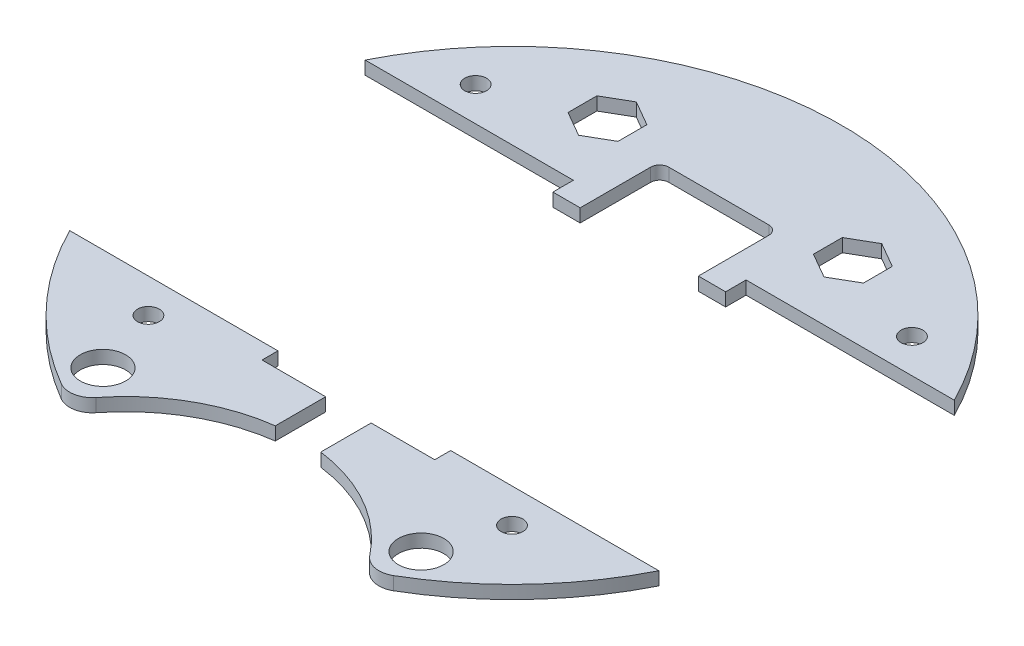
SolidWorks part; units mm, degrees
material "Acrylic (Medium-high impact)"
ref_plane "Front Plane" through (0, 0, 0) normal (0, 0, 1) x (1, 0, 0)
ref_plane "Top Plane" through (0, 0, 0) normal (0, 1, 0) x (1, 0, 0)
ref_plane "Right Plane" through (0, 0, 0) normal (1, 0, 0) x (0, 0, -1)
sketch "Sketch1" plane through (0, 0, 0) normal (0, 1, 0) x (1, 0, 0)
  line L0 (0, -85) -> (-32.4891, -64.8129) construction
  line L1 (0, -85) -> (0, 0) construction
  arc A0 (36.5434, -62.6165) -> (-36.5434, -62.6165) centre (0, 0) ccw
  arc A1 (30.0898, -61.3851) -> (-30.0898, -61.3851) centre (0, -85) ccw
  arc A2 (36.5434, -62.6165) -> (30.0898, -61.3851) centre (34.0231, -58.2982) cw
  arc A3 (-30.0898, -61.3851) -> (-36.5434, -62.6165) centre (-34.0231, -58.2982) cw
  dimension "D1" = 145
  dimension "D2" = 76.5
  dimension "D4" = 5
  dimension "D3" = 85
extrude "Boss-Extrude1" add sketch "Sketch1" along normal blind 2.9
sketch "solenoid placement" plane through (0, 2.9, 0) normal (0, 1, 0) x (1, 0, 0)
  line L4 (-19, -36) -> (19, -36)
  line L5 (-19, 28) -> (-19, -36)
  line L6 (19, 28) -> (-19, 28)
  line L7 (19, -36) -> (19, 28)
  line L8 (-19, -36) -> (19, -36)
  line L9 (-19, 28) -> (-19, -36)
  line L10 (19, 28) -> (-19, 28)
  line L11 (19, -36) -> (19, 28)
  dimension "D1" = 0
extrude "Cut-Extrude1" cut sketch "solenoid placement" against normal through all
sketch "Sketch4" plane through (0, 2.9, 0) normal (0, 1, 0) x (1, 0, 0)
  line L6 (19, 28) -> (-19, 28) construction
  line L10 (-13, 28) -> (13, 28)
  line L11 (13, 28) -> (13, 43.5)
  line L12 (11, 45.5) -> (-11, 45.5)
  line L13 (-13, 43.5) -> (-13, 28)
  arc A5 (13, 43.5) -> (11, 45.5) centre (11, 43.5) ccw
  arc A7 (-11, 45.5) -> (-13, 43.5) centre (-11, 43.5) ccw
  point P10 (0, 28)
  point P11 (0, 28)
  dimension "D3" = 2
  dimension "D1" = 26
  dimension "D2" = 17.5
extrude "Cut-Extrude4" cut sketch "Sketch4" against normal through all
sketch "Sketch5" plane through (0, 2.9, 0) normal (0, 1, 0) x (1, 0, 0)
  line L6 (0, 0) -> (0, 72.5) construction
  line L7 (-21.5, 51.1754) -> (-27, 54.3509)
  line L8 (-27, 54.3509) -> (-32.5, 51.1754)
  line L9 (-32.5, 51.1754) -> (-32.5, 44.8246)
  line L10 (-32.5, 44.8246) -> (-27, 41.6491)
  line L11 (-27, 41.6491) -> (-21.5, 44.8246)
  line L12 (-21.5, 44.8246) -> (-21.5, 51.1754)
  line L13 (21.5, 44.8246) -> (21.5, 51.1754)
  line L14 (27, 41.6491) -> (21.5, 44.8246)
  line L15 (32.5, 44.8246) -> (27, 41.6491)
  line L16 (32.5, 51.1754) -> (32.5, 44.8246)
  line L17 (27, 54.3509) -> (32.5, 51.1754)
  line L18 (21.5, 51.1754) -> (27, 54.3509)
  circle A0 centre (-27, 48) radius 5.5 construction
  arc A1 (36.5434, -62.6165) -> (-36.5434, -62.6165) centre (0, 0) ccw construction
  circle A2 centre (27, 48) radius 5.5 construction
  dimension "D1" = 11
extrude "Cut-Extrude5" cut sketch "Sketch5" against normal through all
sketch "Sketch6" plane through (0, 2.9, 0) normal (0, 1, 0) x (1, 0, 0)
  circle A1 centre (40, -40) radius 2.4
  circle A2 centre (40, -40) radius 2.4
  circle A3 centre (-40, -40) radius 2.4
  circle A4 centre (-40, -40) radius 2.4
  circle A5 centre (48, 40) radius 2.4
  circle A6 centre (48, 40) radius 2.4
  circle A7 centre (-48, 40) radius 2.4
  circle A8 centre (-48, 40) radius 2.4
  dimension "D1" = 0
  dimension "D2" = 0
  dimension "D3" = 0
  dimension "D4" = 0
extrude "Cut-Extrude6" cut sketch "Sketch6" against normal through all
sketch "Sketch3" plane through (0, 2.9, 0) normal (0, 1, 0) x (1, 0, 0)
  line L0 (-19, 28) -> (-19, 32.5)
  line L1 (72.5, -32.5) -> (-72.5, -32.5)
  line L2 (72.5, -32.5) -> (72.5, 32.5)
  line L3 (72.5, 32.5) -> (19, 32.5)
  line L4 (-72.5, -32.5) -> (-72.5, 32.5)
  line L5 (72.5, -32.5) -> (-72.5, 32.5) construction
  line L6 (72.5, 32.5) -> (-72.5, -32.5) construction
  line L7 (-19, 28) -> (19, 28)
  line L8 (19, 28) -> (19, 32.5)
  line L9 (-19, 32.5) -> (-72.5, 32.5)
  arc A0 (36.5434, -62.6165) -> (-36.5434, -62.6165) centre (0, 0) ccw construction
  point P0 (0, 0)
  dimension "D1" = 65
extrude "Cut-Extrude3" cut sketch "Sketch3" against normal through all
sketch "Sketch7" plane through (0, 2.9, 0) normal (0, 1, 0) x (1, 0, 0)
  line L5 (-5, 0) -> (5, 0)
  line L6 (-5, 0) -> (-5, -50)
  line L7 (-5, -50) -> (5, -50)
  line L8 (5, 0) -> (5, -50)
  point P4 (0, 0)
  dimension "D1" = 10
  dimension "D2" = 50
extrude "Cut-Extrude7" cut sketch "Sketch7" against normal through all
sketch "Sketch9" plane through (0, 2.9, 0) normal (0, -1, 0) x (1, 0, 0)
  circle A1 centre (35, 55) radius 5
  circle A2 centre (35, 55) radius 5
  circle A3 centre (-35, 55) radius 5
  circle A4 centre (-35, 55) radius 5
  dimension "D1" = 0
  dimension "D2" = 0
extrude "Cut-Extrude11" cut sketch "Sketch9" along normal through all
equation "\"smallPulleyTeeth\"= 15"
equation "\"largePulleyTeeth\"= 30"
equation "\"eighthThick\"= 2.9mm"
equation "\"sixteenthThick\" = 1.7mm"
equation "\"quarterThick\"=6.0mm"
equation "\"OD\" = 145mm"
equation "\"puckAngle\" = 60.5deg"
equation "\"D1@Sketch1\"=\"OD\""
equation "\"puckDiam\" = 76.5mm"
equation "\"D2@Sketch1\"=\"puckDiam\""
equation "\"D1@Boss-Extrude1\"=\"eighthThick\""
equation "\"axlePress\" = 5.9mm"
equation "\"press\" = 0.2mm"
equation "\"wheelClear\" = 0.3mm"
equation "\"10-32clear\" = 4.8mm"
equation "\"6-32clear\" = 3.3mm"
equation "\"8-32clear\" = 4.0mm"
equation "\"wheelHeight\" = 22mm"
equation "\"wheelWell\" = 65mm"
equation "\"D1@Sketch3\"=\"wheelWell\""
equation "\"puckDist\" = 85mm"
equation "\"scoopFillet\" = 5mm"
equation "\"4-40clear\" = 3.0mm"
equation "\"D3@Sketch1\"=\"puckDist\""
equation "\"D4@Sketch1\"=\"scoopFillet\""
